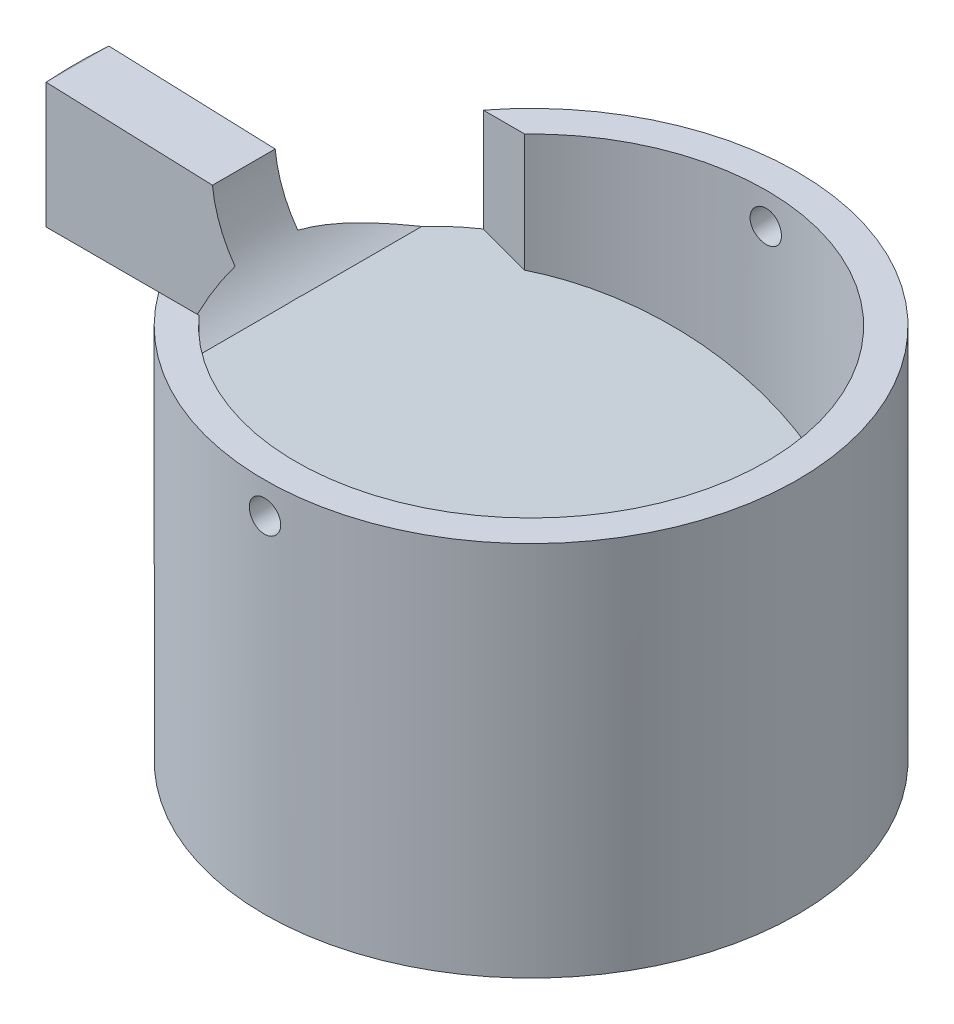
SolidWorks part; units mm, degrees
ref_plane "Front Plane" through (0, 0, 0) normal (0, 0, 1) x (1, 0, 0)
ref_plane "Top Plane" through (0, 0, 0) normal (0, 1, 0) x (1, 0, 0)
ref_plane "Right Plane" through (0, 0, 0) normal (1, 0, 0) x (0, 0, -1)
sketch "Sketch1" plane through (0, 0, 0) normal (0, 1, 0) x (1, 0, 0)
  circle A0 centre (0, 0) radius 9.525
  circle A1 centre (0, 0) radius 10.795
  dimension "D1" = 19.05
  dimension "D2" = 1.27
extrude "Boss-Extrude1" add sketch "Sketch1" along normal blind 2.54 contours A1
sketch "Sketch2" plane through (0, 2.54, 0) normal (0, 1, 0) x (1, 0, 0)
  circle A0 centre (0, 0) radius 9.525
  circle A1 centre (0, 0) radius 10.795
  circle A2 centre (0, 0) radius 10.795 construction
  dimension "D1" = 19.05
extrude "Boss-Extrude2" add sketch "Sketch2" along normal blind 12.7
ref_plane "Plane1" through (0, 12.7, 0) normal (0, 1, 0) x (1, 0, 0)
sketch "Sketch3" plane through (0, 0, 0) normal (0, 0, 1) x (1, 0, 0)
  line L1 (9.525, 2.54) -> (-9.525, 2.54) construction
  line L2 (-9.525, 11.43) -> (-9.525, 2.54)
  line L3 (-9.525, 2.54) -> (9.525, 2.54)
  line L4 (-9.525, 11.43) -> (9.525, 4.5134)
  line L5 (9.525, 4.5134) -> (9.525, 2.54)
  dimension "D1" = 8.89
  dimension "D2" = 1.9734
extrude "Boss-Extrude3" add sketch "Sketch3" along normal mid plane 19.05 contours L2 L3 L5 L4
sketch "Sketch4" plane through (0, 15.24, 0) normal (0, 1, 0) x (1, 0, 0)
  circle A0 centre (0, 0) radius 10.795
  circle A1 centre (0, 0) radius 13.4704
  circle A2 centre (0, 0) radius 10.795 construction
extrude "Cut-Extrude1" cut sketch "Sketch4" against normal up to surface (15.24 mm away) up to face at (0, 0, 10.795)
sketch "Sketch5" plane through (0, 15.24, 0) normal (0, 1, 0) x (1, 0, 0)
  line L0 (0, 0) -> (-16.3634, 0) construction
  line L2 (-9.525, 1.27) -> (-18.3712, 1.27)
  line L3 (-9.525, 1.27) -> (-9.525, -1.27)
  line L4 (-9.525, -1.27) -> (-18.3712, -1.27)
  arc A0 (-18.3712, 1.27) -> (-18.3712, -1.27) centre (0, 0) ccw
  circle A1 centre (0, 0) radius 10.795 construction
  dimension "D1" = 7.62
  dimension "D2" = 1.27
  dimension "D3" = 1.27
  dimension "D4" = 9.525
extrude "Boss-Extrude4" add sketch "Sketch5" against normal blind 5.08
sketch "Sketch7" plane through (0, 0, -1.27) normal (0, 0, -1) x (-1, 0, 0)
  line L0 (18.3712, 13.6281) -> (18.3712, 15.24)
  line L2 (18.3712, 15.24) -> (8.9498, 14.8981)
  line L6 (10.72, 15.24) -> (18.3712, 15.24) construction
  line L7 (18.3712, 10.16) -> (18.3712, 15.24) construction
  line L9 (18.3712, 15.24) -> (8.9801, 16.51)
  line L14 (8.9801, 16.51) -> (8.9498, 14.8981)
  dimension "D1" = 1.6119
  dimension "D2" = 0
  dimension "D3" = 0
  dimension "D4" = 1.6119
extrude "Cut-Extrude6" cut sketch "Sketch7" against normal blind 3.81 and the other way blind 1.27 contours L2 L14 L9
fillet "Fillet1" radius 2.54 2 edges at (-9.836, 15.24, -2.54) (-9.836, 15.24, 2.54)
ref_plane "Plane2" through (0, 0, 0) normal (0, 0, -1) x (-1, 0, 0)
ref_plane "Plane3" through (0, 0, -6.604) normal (0, 0, -1) x (-1, 0, 0)
sketch "Sketch8" plane through (0, 0, 0) normal (0, 0, 1) x (1, 0, 0)
  line L0 (-10.606, 14.9582) -> (10.795, 14.9582) construction
  line L1 (-10.4919, 14.9541) -> (-10.72, 14.9623) construction
  line L2 (10.795, 0) -> (10.795, 15.24) construction
  line L3 (0, -15.24) -> (0, 15.24) construction
  line L4 (10.795, 15.24) -> (-10.1269, 15.24) construction
  line L5 (9.525, 15.24) -> (-8.7213, 15.24) construction
  circle A0 centre (0, 13.97) radius 0.635
  point P12 (0, 0)
  dimension "D2" = 1.27
  dimension "D1" = 1.27
extrude "Cut-Extrude7" cut sketch "Sketch8" against normal through all both and the other way through all
sketch "Sketch9" plane through (0, 0, -6.604) normal (0, 0, -1) x (-1, 0, 0)
  line L1 (9.525, 11.43) -> (-9.525, 4.5134) construction
  line L3 (11.6344, 14.9955) -> (5.6712, 16.0646)
  line L4 (9.5183, 11.4276) -> (7.1376, 10.5632)
  line L5 (7.1376, 10.5632) -> (5.6712, 10.0308)
  line L6 (5.6712, 16.0646) -> (5.6712, 10.0308)
  line L7 (18.3712, 10.16) -> (18.3712, 15.24) construction
  line L8 (10.72, 10.16) -> (10.72, 14.9623) construction
  line L9 (10.72, 14.9623) -> (18.3712, 15.24) construction
  arc A0 (11.6344, 14.9955) -> (9.5183, 11.4276) centre (6.6917, 15.5155) cw
  point P4 (5.6641, 16.0951)
  point P5 (0, 0)
  point P15 (0, 0)
  dimension "D1" = 12.7
  dimension "D2" = 0.9144
extrude "Cut-Extrude8" cut sketch "Sketch9" against normal blind 12.954 contours L3 L6 L5 L4 A0
equation "\"D1@Sketch9\"=\"D1@Sketch5\" + .2"
